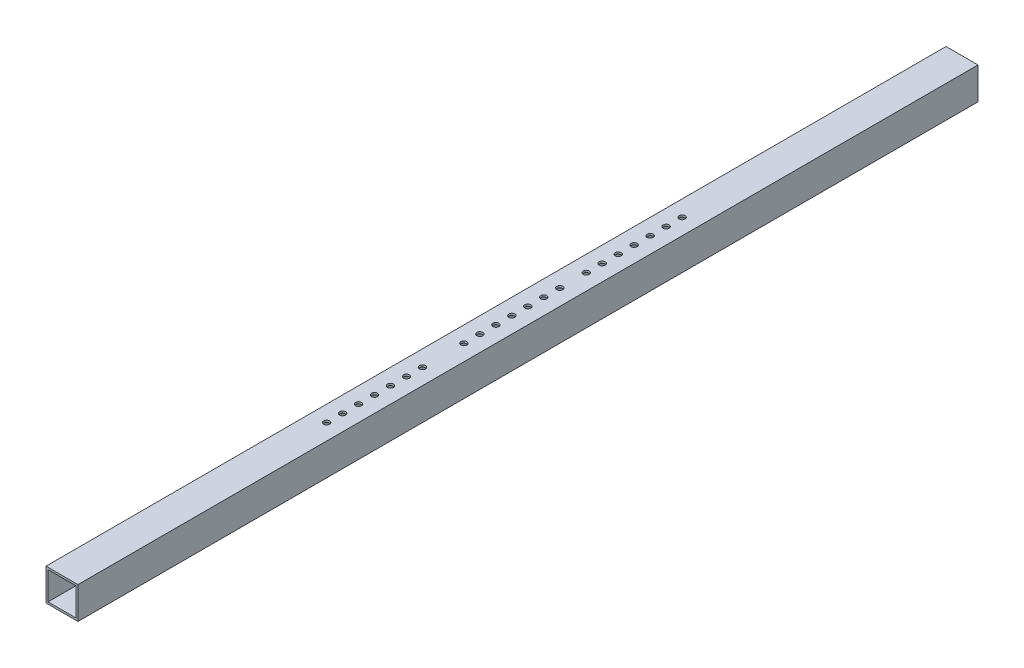
SolidWorks part; units mm, degrees
material "ALUMINUM 6061-T6"
ref_plane "Front Plane" through (0, 0, 0) normal (0, 0, 1) x (1, 0, 0)
ref_plane "Top Plane" through (0, 0, 0) normal (0, 1, 0) x (1, 0, 0)
ref_plane "Right Plane" through (0, 0, 0) normal (1, 0, 0) x (0, 0, -1)
sketch "Sketch1" plane through (0, 0, 0) normal (0, 0, 1) x (1, 0, 0)
  line L0 (11.1125, -11.1125) -> (11.1125, 11.1125)
  line L1 (-12.7, -12.7) -> (12.7, -12.7)
  line L2 (-12.7, -12.7) -> (-12.7, 12.7)
  line L3 (-12.7, 12.7) -> (12.7, 12.7)
  line L4 (12.7, -12.7) -> (12.7, 12.7)
  line L5 (-12.7, -12.7) -> (12.7, 12.7) construction
  line L6 (-12.7, 12.7) -> (12.7, -12.7) construction
  line L7 (-11.1125, 11.1125) -> (11.1125, 11.1125)
  line L8 (-11.1125, -11.1125) -> (-11.1125, 11.1125)
  line L9 (-11.1125, -11.1125) -> (11.1125, -11.1125)
  point P0 (0, 0)
  dimension "D1" = 25.4
  dimension "D2" = 25.4
  dimension "D3" = 1.5875
extrude "Boss-Extrude1" add sketch "Sketch1" along normal mid plane 715.518
sketch "Sketch2" plane through (0, -12.7, 0) normal (0, -1, 0) x (1, 0, 0)
  line L0 (-12.7, 357.759) -> (12.7, 357.759) construction
  circle A0 centre (0, -37.973) radius 2.3812
  circle A1 centre (0, -25.273) radius 2.3812
  circle A2 centre (0, -12.573) radius 2.3812
  circle A3 centre (0, 0.127) radius 2.3812
  circle A4 centre (0, 12.827) radius 2.3812
  circle A5 centre (0, 25.527) radius 2.3812
  circle A6 centre (0, 38.227) radius 2.3812
  dimension "D1" = 4.7625
  dimension "D2" = 12.7
  dimension "D3" = 12.7
  dimension "D4" = 12.7
  dimension "D5" = 12.7
  dimension "D6" = 12.7
  dimension "D7" = 12.7
  dimension "D8" = 357.632
extrude "Cut-Extrude1" cut sketch "Sketch2" against normal through all
sketch "Sketch3" plane through (0, -12.7, 0) normal (0, -1, 0) x (1, 0, 0)
  line L0 (-12.7, 357.759) -> (12.7, 357.759) construction
  circle A0 centre (0, 71.1814) radius 2.3812
  circle A1 centre (0, 83.8814) radius 2.3812
  circle A2 centre (0, 96.5814) radius 2.3812
  circle A3 centre (0, 121.9814) radius 2.3812
  circle A4 centre (0, 134.6814) radius 2.3812
  circle A5 centre (0, 147.3814) radius 2.3812
  circle A6 centre (0, 109.2814) radius 2.3812
  circle A7 centre (0, -59.0186) radius 2.3812
  circle A8 centre (0, -71.7186) radius 2.3812
  circle A9 centre (0, -84.4186) radius 2.3812
  circle A10 centre (0, -97.1186) radius 2.3812
  circle A11 centre (0, -109.8186) radius 2.3812
  circle A12 centre (0, -122.5186) radius 2.3812
  circle A13 centre (0, -135.2186) radius 2.3812
  point P32 (0.3423, -108.6102)
  dimension "D1" = 4.7625
  dimension "D9" = 4.7625
  dimension "D10" = 12.7
  dimension "D11" = 12.7
  dimension "D12" = 12.7
  dimension "D13" = 12.7
  dimension "D14" = 12.7
  dimension "D15" = 12.7
  dimension "D16" = 454.8776
  dimension "D2" = 12.7
  dimension "D3" = 12.7
  dimension "D4" = 12.7
  dimension "D5" = 12.7
  dimension "D6" = 12.7
  dimension "D7" = 12.7
  dimension "D8" = 248.4776
extrude "Cut-Extrude2" cut sketch "Sketch3" against normal through all
